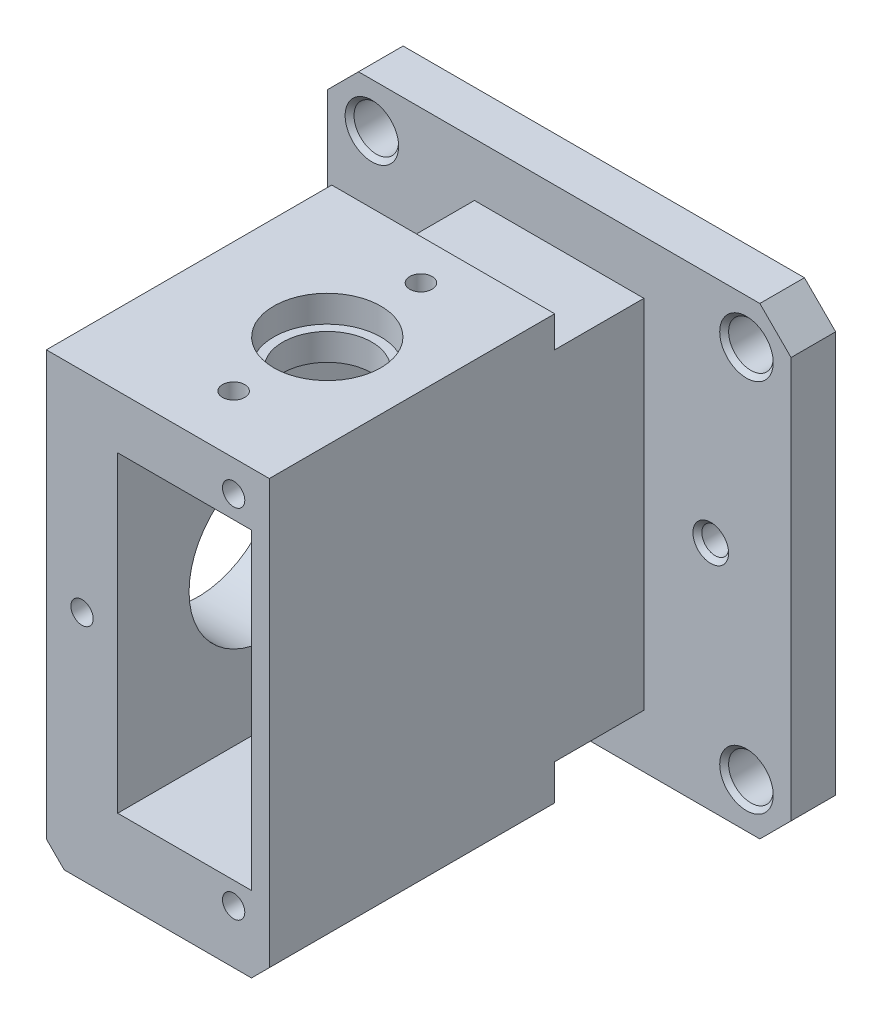
SolidWorks part; units mm, degrees
material "Сталь"
ref_plane "Спереди" through (0, 0, 0) normal (0, 0, 1) x (1, 0, 0)
ref_plane "Сверху" through (0, 0, 0) normal (0, 1, 0) x (1, 0, 0)
ref_plane "Справа" through (0, 0, 0) normal (1, 0, 0) x (0, 0, -1)
sketch "Эскиз1" plane through (0, 0, 0) normal (0, 0, 1) x (1, 0, 0)
  line L1 (-26, -26) -> (26, -26)
  line L2 (-26, -26) -> (-26, 26)
  line L3 (-26, 26) -> (26, 26)
  line L4 (26, -26) -> (26, 26)
  line L5 (-26, -26) -> (26, 26) construction
  line L6 (-26, 26) -> (26, -26) construction
  point P0 (0, 0)
  dimension "D1" = 52
extrude "Бобышка-Вытянуть1" add sketch "Эскиз1" along normal blind 5
sketch "Эскиз2" plane through (0, 0, 5) normal (0, 0, 1) x (1, 0, 0)
  line L1 (-21, -21) -> (21, -21)
  line L2 (-21, -21) -> (-21, 21)
  line L3 (-21, 21) -> (21, 21)
  line L4 (21, -21) -> (21, 21)
  line L5 (-21, -21) -> (21, 21) construction
  line L6 (-21, 21) -> (21, -21) construction
  circle A0 centre (21, 21) radius 2.5
  circle A1 centre (21, -21) radius 2.5
  circle A2 centre (-21, -21) radius 2.5
  circle A3 centre (-21, 21) radius 2.5
  point P0 (0, 0)
  dimension "D2" = 5
  dimension "D1" = 42
extrude "Вырез-Вытянуть1" cut sketch "Эскиз2" against normal through all contours L3 A3 L2 | L4 A0 L3 | L3 A0 L4 | L2 A3 L3 | L2 A2 L1 | L1 A2 L2 | L1 A1 L4 | L4 A1 L1 | A2 region at (-19.939, -19.939, 5) region at (-21.3537, -21.3537, 5) region at (19.939, -19.939, 5) region at (21.3537, -21.3537, 5) region at (-21.3537, 21.3537, 5) region at (-19.939, 19.939, 5) region at (19.939, 19.939, 5) region at (21.3537, 21.3537, 5)
chamfer "Фаска1" distance 3.5 angle 45 4 edges at (-26, 26, 2.5) (26, 26, 2.5) (26, -26, 2.5) (-26, -26, 2.5)
chamfer "Фаска2" distance 0.5 angle 45 4 edges at (23.5, -21, 5) (23.5, 21, 5) (-18.5, 21, 5) (-18.5, -21, 5)
sketch "Эскиз3" plane through (0, 0, 5) normal (0, 0, 1) x (1, 0, 0)
  line L0 (-26, 0) -> (26, 0) construction
  line L1 (-26, 22.5) -> (-26, -22.5) construction
  line L2 (26, -22.5) -> (26, 22.5) construction
  line L4 (9.5, -20) -> (-9.5, -20)
  line L5 (9.5, -20) -> (9.5, 20)
  line L6 (9.5, 20) -> (-9.5, 20)
  line L7 (-9.5, -20) -> (-9.5, 20)
  line L8 (9.5, -20) -> (-9.5, 20) construction
  line L9 (9.5, 20) -> (-9.5, -20) construction
  point P6 (0, 0)
  dimension "D1" = 19
  dimension "D2" = 40
extrude "Бобышка-Вытянуть2" add sketch "Эскиз3" along normal blind 42
sketch "Эскиз6" plane through (0, 0, 47) normal (0, 0, 1) x (1, 0, 0)
  line L1 (-7.5, -17.5) -> (7.5, -17.5)
  line L2 (-7.5, -17.5) -> (-7.5, 17.5)
  line L3 (-7.5, 17.5) -> (7.5, 17.5)
  line L4 (7.5, -17.5) -> (7.5, 17.5)
  line L5 (-7.5, -17.5) -> (7.5, 17.5) construction
  line L6 (-7.5, 17.5) -> (7.5, -17.5) construction
  point P0 (0, 0)
  dimension "D1" = 15
  dimension "D2" = 35
sketch "Эскиз4" plane through (0, 0, 47) normal (0, 0, 1) x (1, 0, 0)
  line L0 (22.5, 26) -> (-22.5, 26) construction
  line L1 (-15.5, -26) -> (9.5, -26)
  line L2 (-15.5, -26) -> (-15.5, 26)
  line L3 (-15.5, 26) -> (9.5, 26)
  line L4 (9.5, -26) -> (9.5, 26)
  line L5 (-15.5, -26) -> (9.5, 26) construction
  line L6 (-15.5, 26) -> (9.5, -26) construction
  line L7 (9.5, -20) -> (9.5, 20) construction
  point P0 (-3, 0)
  dimension "D1" = 25
extrude "Бобышка-Вытянуть3" add sketch "Эскиз4" against normal blind 32
extrude "Вырез-Вытянуть2" cut sketch "Эскиз6" against normal through all
sketch "Эскиз7" plane through (-15.5, 0, 0) normal (-1, 0, 0) x (0, 0, 1)
  line L0 (15, 26) -> (15, -26) construction
  circle A0 centre (30, 0) radius 9
  dimension "D1" = 18
  dimension "D2" = 15
extrude "Вырез-Вытянуть3" cut sketch "Эскиз7" against normal up to next
sketch "Эскиз8" plane through (-15.5, 0, 0) normal (-1, 0, 0) x (0, 0, 1)
  line L1 (21, 11) -> (39, 11) construction
  line L2 (21, 11) -> (21, -11) construction
  line L3 (21, -11) -> (39, -11) construction
  line L4 (39, 11) -> (39, -11) construction
  line L5 (21, 11) -> (39, -11) construction
  line L6 (21, -11) -> (39, 11) construction
  point P0 (30, 0)
  dimension "D1" = 18
  dimension "D2" = 22
hole_wizard "Отверстие обработанное метчиком M3x0.51" positions "Трехмерный эскиз1" profile "Эскиз9" tap size "M3x0.5" standard "Ansi Metric"
sketch3d "Трехмерный эскиз1"
  point P0 (-15.5, 11, 39)
  point P3 (-15.5, -11, 39)
  point P6 (-15.5, -11, 21)
  point P9 (-15.5, 11, 21)
sketch "Эскиз9" plane through (-15.5, 11, 39) normal (0, 1, 0) x (0, 0, 1)
  line L0 (0, 0) -> (0, 6.2511)
  line L1 (0, 6.2511) -> (1.25, 5.5)
  line L2 (1.25, 5.5) -> (1.25, 0)
  line L5 (1.25, 0) -> (0, 0)
  line L10 (0, 6.2511) -> (-1.25, 5.5) construction
  line L11 (0, -6.35) -> (0, 107.95) construction
  dimension "Диаметр сверла" = 2.5
  dimension "Глубина сверла" = 5.5
  dimension "Угол заточки сверла" = 118
cosmetic thread "Отверстие резьбы1" parameters "D1"=4, "D2"=3
cosmetic thread "Отверстие резьбы2" parameters "D1"=4, "D2"=3
cosmetic thread "Отверстие резьбы3" parameters "D1"=4, "D2"=3
cosmetic thread "Отверстие резьбы4" parameters "D1"=4, "D2"=3
chamfer "Фаска3" distance 2 angle 45 4 edges at (9.5, -26, 31) (9.5, 26, 31) (-15.5, 26, 31) (-15.5, -26, 31)
sketch "Эскиз11" plane through (0, 0, 47) normal (0, 0, 1) x (1, 0, 0)
  point P0 (5.5, 20)
  point P1 (-11.5, 0)
  point P3 (5.5, -20)
hole_wizard "Отверстие обработанное метчиком M3x0.52" positions "Трехмерный эскиз3" profile "Эскиз12" tap size "M3x0.5" standard "Ansi Metric"
sketch3d "Трехмерный эскиз3"
  point P0 (5.5, 20, 47)
  point P3 (-11.5, 0, 47)
  point P6 (5.5, -20, 47)
sketch "Эскиз12" plane through (5.5, 20, 47) normal (1, 0, 0) x (0, -1, 0)
  line L0 (0, 0) -> (0, 6.2511)
  line L1 (0, 6.2511) -> (1.25, 5.5)
  line L2 (1.25, 5.5) -> (1.25, 0)
  line L5 (1.25, 0) -> (0, 0)
  line L10 (0, 6.2511) -> (-1.25, 5.5) construction
  line L11 (0, -6.35) -> (0, 107.95) construction
  dimension "Диаметр сверла" = 2.5
  dimension "Глубина сверла" = 5.5
  dimension "Угол заточки сверла" = 118
cosmetic thread "Отверстие резьбы5" parameters "D1"=4, "D2"=3
cosmetic thread "Отверстие резьбы6" parameters "D1"=4, "D2"=3
cosmetic thread "Отверстие резьбы7" parameters "D1"=4, "D2"=3
sketch "Эскиз13" plane through (0, -26, 0) normal (0, -1, 0) x (-1, 0, 0)
  line L0 (26, 0) -> (26, -5) construction
  line L1 (22.5, 0) -> (-22.5, 0) construction
  circle A0 centre (1, -30) radius 3.1
  dimension "D3" = 6.2
  dimension "D1" = 25
  dimension "D2" = 30
extrude "Вырез-Вытянуть4" cut sketch "Эскиз13" against normal blind 7
sketch "Эскиз14" plane through (0, -19, 0) normal (0, -1, 0) x (1, 0, 0)
  circle A0 centre (-1, 30) radius 1.55
  dimension "D1" = 3.1
extrude "Вырез-Вытянуть5" cut sketch "Эскиз14" against normal up to next
chamfer "Фаска4" distance 1 angle 45 1 edges at (-1, -26, 26.9)
sketch "Эскиз15" plane through (0, 26, 0) normal (0, 1, 0) x (1, 0, 0)
  line L1 (-15.5, -47) -> (9.5, -47)
  line L2 (-15.5, -47) -> (-15.5, -15)
  line L3 (-15.5, -15) -> (9.5, -15)
  line L4 (9.5, -47) -> (9.5, -15)
extrude "Вырез-Вытянуть6" cut sketch "Эскиз15" against normal blind 2.5
sketch "Эскиз16" plane through (0, 23.5, 0) normal (0, 1, 0) x (1, 0, 0)
  circle A0 centre (-1, -30) radius 6
  dimension "D1" = 12
extrude "Вырез-Вытянуть7" cut sketch "Эскиз16" against normal blind 3
sketch "Эскиз17" plane through (0, 20.5, 0) normal (0, 1, 0) x (1, 0, 0)
  circle A0 centre (-1, -30) radius 5
  dimension "D1" = 10
extrude "Вырез-Вытянуть8" cut sketch "Эскиз17" against normal up to next
sketch "Эскиз18" plane through (0, 23.5, 0) normal (0, 1, 0) x (1, 0, 0)
  line L0 (-1, -30) -> (-1, -47) construction
  line L1 (-15.5, -47) -> (9.5, -47) construction
  line L2 (-1, -30) -> (-1, -15) construction
  line L3 (9.5, -15) -> (-15.5, -15) construction
  point P5 (-1, -40.5)
  point P9 (-1, -19.5)
  dimension "D1" = 10.5
  dimension "D2" = 10.5
hole_wizard "Отверстие обработанное метчиком M3x0.53" positions "Трехмерный эскиз4" profile "Эскиз19" tap size "M3x0.5" standard "Ansi Metric"
sketch3d "Трехмерный эскиз4"
  point P0 (-1, 23.5, 40.5)
  point P3 (-1, 23.5, 19.5)
sketch "Эскиз19" plane through (-1, 23.5, 40.5) normal (1, 0, 0) x (0, 0, 1)
  line L0 (0, 0) -> (0, 5.2511)
  line L1 (0, 5.2511) -> (1.25, 4.5)
  line L2 (1.25, 4.5) -> (1.25, 0)
  line L5 (1.25, 0) -> (0, 0)
  line L10 (0, 5.2511) -> (-1.25, 4.5) construction
  line L11 (0, -6.35) -> (0, 107.95) construction
  dimension "Диаметр сверла" = 2.5
  dimension "Глубина сверла" = 4.5
  dimension "Угол заточки сверла" = 118
cosmetic thread "Отверстие резьбы8" parameters "D1"=3.5, "D2"=3
cosmetic thread "Отверстие резьбы9" parameters "D1"=3.5, "D2"=3
sketch "Эскиз20" plane through (0, 0, 0) normal (0, 0, -1) x (-1, 0, 0)
  line L0 (-26, 0) -> (26, 0) construction
  line L1 (-26, -22.5) -> (-26, 22.5) construction
  line L2 (26, 22.5) -> (26, -22.5) construction
  circle A0 centre (-17, 0) radius 1.5
  circle A1 centre (17, 0) radius 1.5
  dimension "D1" = 3
  dimension "D2" = 9
  dimension "D3" = 9
extrude "Вырез-Вытянуть9" cut sketch "Эскиз20" against normal up to next
chamfer "Фаска5" distance 0.5 angle 45 2 edges at (15.5, 0, 5) (-18.5, 0, 5)
